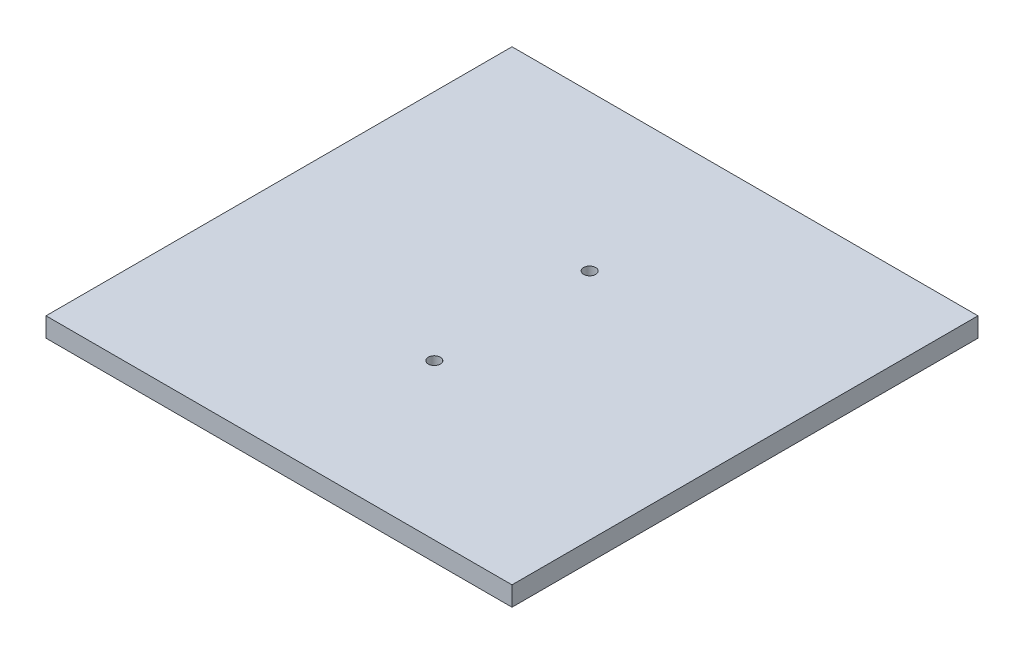
SolidWorks part; units mm, degrees
ref_plane "Piano frontale" through (0, 0, 0) normal (0, 0, 1) x (1, 0, 0)
ref_plane "Piano superiore" through (0, 0, 0) normal (0, 1, 0) x (1, 0, 0)
ref_plane "Piano destro" through (0, 0, 0) normal (1, 0, 0) x (0, 0, -1)
sketch "Schizzo1" plane through (0, 0, 0) normal (0, 1, 0) x (1, 0, 0)
  line L1 (-47.6798, -40.232) -> (72.3202, -40.232)
  line L2 (-47.6798, -40.232) -> (-47.6798, 79.768)
  line L3 (-47.6798, 79.768) -> (72.3202, 79.768)
  line L4 (72.3202, -40.232) -> (72.3202, 79.768)
  dimension "D1" = 120
  dimension "D2" = 120
extrude "Estrusione-Estrusione1" add sketch "Schizzo1" along normal blind 5
sketch "Schizzo2" plane through (0, 0, 0) normal (0, -1, 0) x (1, 0, 0)
  line L0 (12.3202, -79.768) -> (12.3202, 40.232) construction
  line L3 (72.3202, -79.768) -> (-47.6798, -79.768) construction
  line L5 (-47.6798, 40.232) -> (72.3202, 40.232) construction
  line L6 (12.3202, -19.768) -> (72.3202, -19.768) construction
  line L7 (72.3202, 40.232) -> (72.3202, -79.768) construction
  point P6 (12.3202, 0.232)
  point P12 (12.3202, -39.768)
  point P16 (-73.7744, 52.4306)
  dimension "D1" = 20
  dimension "D2" = 20
  dimension "D3" = 60
hole_wizard "Foro per Vite M2.5-1" positions "Schizzo3D1" profile "Schizzo7" hole size "M2.5" standard "IS" end condition through all
sketch3d "Schizzo3D1"
  point P0 (12.3202, 0, 0.232)
  point P3 (12.3202, 0, -39.768)
sketch "Schizzo7" plane through (12.3202, 0, 0.232) normal (1, 0, 0) x (0, 0, -1)
  line L0 (0, 0) -> (0, 5)
  line L1 (0, 5) -> (1.55, 5)
  line L2 (1.55, 5) -> (1.55, 0)
  line L5 (1.55, 0) -> (0, 0)
  line L11 (0, -6.35) -> (0, 107.95) construction
  dimension "Thru Hole Dia." = 3.1
  dimension "Thru Hole Depth" = 5
